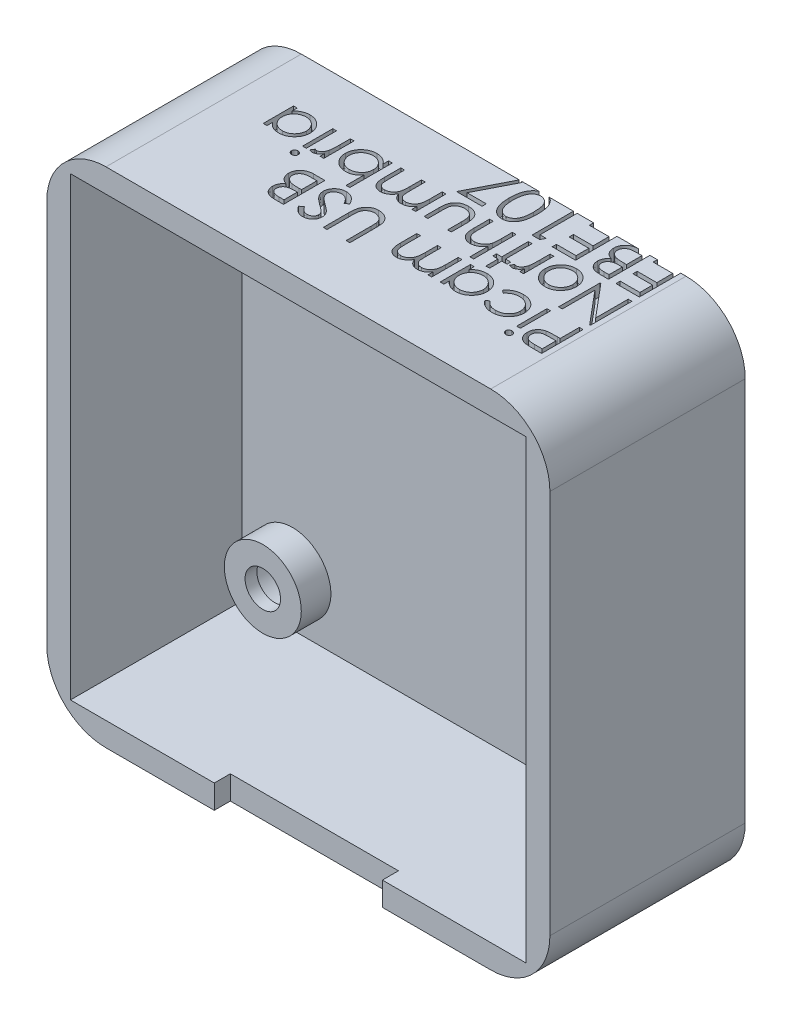
SolidWorks part; units mm, degrees
ref_plane "Front Plane" through (0, 0, 0) normal (0, 0, 1) x (1, 0, 0)
ref_plane "Top Plane" through (0, 0, 0) normal (0, 1, 0) x (1, 0, 0)
ref_plane "Right Plane" through (0, 0, 0) normal (1, 0, 0) x (0, 0, -1)
sketch "Sketch1" plane through (0, 0, 0) normal (0, 0, 1) x (1, 0, 0)
  line L1 (-20.25, -20.25) -> (20.25, -20.25)
  line L2 (-20.25, -20.25) -> (-20.25, 20.25)
  line L3 (-20.25, 20.25) -> (20.25, 20.25)
  line L4 (20.25, -20.25) -> (20.25, 20.25)
  line L5 (-20.25, -20.25) -> (20.25, 20.25) construction
  line L6 (-20.25, 20.25) -> (20.25, -20.25) construction
  point P0 (0, 0)
extrude "Boss-Extrude1" add sketch "Sketch1" along normal blind 2
sketch "Sketch2" plane through (0, 0, 2) normal (0, 0, 1) x (1, 0, 0)
  circle A0 centre (-15, 15) radius 1.25
  circle A1 centre (15, -15) radius 1.25
  circle A2 centre (15, 16.25) radius 1.25
  circle A3 centre (-15, -15) radius 1.25
extrude "Cut-Extrude1" cut sketch "Sketch2" against normal blind 2 contours A3 | A1 | A2 | A0
sketch "Sketch3" plane through (0, 0, 2) normal (0, 0, 1) x (1, 0, 0)
  line L0 (20.25, 20.25) -> (-20.25, 20.25) construction
  line L5 (-19.25, -19.25) -> (19.25, 19.25) construction
  line L6 (-19.25, 19.25) -> (19.25, -19.25) construction
  line L7 (21.25, -21.25) -> (-21.25, -21.25)
  line L8 (21.25, -21.25) -> (21.25, 21.25)
  line L9 (21.25, 21.25) -> (-21.25, 21.25)
  line L10 (-21.25, -21.25) -> (-21.25, 21.25)
  line L11 (21.25, -21.25) -> (-21.25, 21.25) construction
  line L12 (21.25, 21.25) -> (-21.25, -21.25) construction
  line L13 (20.25, -20.25) -> (-20.25, -20.25)
  line L14 (20.25, -20.25) -> (20.25, 20.25)
  line L15 (20.25, 20.25) -> (-20.25, 20.25)
  line L16 (-20.25, -20.25) -> (-20.25, 20.25)
  line L17 (20.25, -20.25) -> (-20.25, 20.25) construction
  line L18 (20.25, 20.25) -> (-20.25, -20.25) construction
  point P0 (0, 0)
  point P6 (0, 0)
  point P11 (0, 0)
extrude "Boss-Extrude2" add sketch "Sketch3" against normal blind 2
sketch "Sketch4" plane through (0, 0, 2) normal (0, 0, 1) x (1, 0, 0)
  line L1 (21.25, -21.25) -> (-21.25, -21.25)
  line L2 (21.25, -21.25) -> (21.25, 21.25)
  line L3 (21.25, 21.25) -> (-21.25, 21.25)
  line L4 (-21.25, -21.25) -> (-21.25, 21.25)
  line L5 (21.25, -21.25) -> (-21.25, 21.25) construction
  line L6 (21.25, 21.25) -> (-21.25, -21.25) construction
  line L7 (19.25, -19.25) -> (-19.25, -19.25)
  line L8 (19.25, -19.25) -> (19.25, 19.25)
  line L9 (19.25, 19.25) -> (-19.25, 19.25)
  line L10 (-19.25, -19.25) -> (-19.25, 19.25)
  line L11 (19.25, -19.25) -> (-19.25, 19.25) construction
  line L12 (19.25, 19.25) -> (-19.25, -19.25) construction
  point P0 (0, 0)
  point P7 (0, 0)
extrude "Boss-Extrude3" add sketch "Sketch4" along normal blind 14.5
sketch "Sketch6" plane through (0, 0, 2) normal (0, 0, 1) x (1, 0, 0)
  circle A0 centre (-15, 15) radius 2.25
  circle A1 centre (-15, 15) radius 3.25
  circle A3 centre (15, 15) radius 3.25
  circle A4 centre (15, 16.25) radius 1.25 construction
  circle A5 centre (15, 15) radius 2.25
  circle A6 centre (-15, -15) radius 2.25
  circle A7 centre (-15, -15) radius 3.25
  circle A8 centre (15, -15) radius 2.25
  circle A9 centre (15, -15) radius 3.25
extrude "Boss-Extrude4" add sketch "Sketch6" along normal blind 2.5
sketch "Sketch7" plane through (0, 0, 0) normal (0, 0, -1) x (-1, 0, 0)
  circle A0 centre (-15, 16.25) radius 1.25
extrude "Boss-Extrude5" add sketch "Sketch7" against normal blind 2
sketch "Sketch8" plane through (0, 0, 2) normal (0, 0, 1) x (1, 0, 0)
  circle A0 centre (15, 15) radius 1.25
extrude "Cut-Extrude2" cut sketch "Sketch8" against normal blind 2
sketch "Sketch10" plane through (0, 0, 4.5) normal (0, 0, 1) x (1, 0, 0)
  circle A0 centre (-15, 15) radius 2.25
  circle A1 centre (15, 15) radius 2.25
  circle A2 centre (15, 15) radius 1.25
  circle A3 centre (-15, 15) radius 1.25
  circle A4 centre (-15, -15) radius 1.25
  circle A5 centre (-15, -15) radius 2.25
  circle A6 centre (15, -15) radius 1.25
  circle A7 centre (15, -15) radius 2.25
extrude "Boss-Extrude6" add sketch "Sketch10" against normal blind 1
sketch "Sketch11" plane through (0, 0, 0) normal (0, 0, -1) x (-1, 0, 0)
  circle A0 centre (-15, 15) radius 2.25
  circle A1 centre (15, 15) radius 2.25
  circle A2 centre (15, -15) radius 2.25
  circle A3 centre (-15, -15) radius 2.25
extrude "Cut-Extrude3" cut sketch "Sketch11" against normal blind 3.5
sketch "Sketch12" plane through (0, 0, 0) normal (0, 0, -1) x (-1, 0, 0)
  line L11 (-10.8, 15.2) -> (-3.3, 15.2)
  line L12 (-10.8, 15.2) -> (-10.8, 11.7)
  line L13 (-10.8, 11.7) -> (-3.3, 11.7)
  line L14 (-3.3, 15.2) -> (-3.3, 11.7)
  point P0 (0, 0)
extrude "Cut-Extrude4" cut sketch "Sketch12" against normal blind 3.5
sketch "Sketch13" plane through (0, 0, 0) normal (0, 0, -1) x (-1, 0, 0)
  line L4 (-11.05, 11.45) -> (-3.05, 11.45)
  line L5 (-11.05, 11.45) -> (-11.05, 15.45)
  line L6 (-11.05, 15.45) -> (-3.05, 15.45)
  line L7 (-3.05, 11.45) -> (-3.05, 15.45)
  point P4 (-7.05, 13.45)
extrude "Cut-Extrude5" cut sketch "Sketch13" against normal blind 3.5 contours L6 L7 L4 L5
sketch "Sketch14" plane through (0, 0, 0) normal (0, 0, -1) x (-1, 0, 0)
  circle A0 centre (14, 7) radius 1.5
  point P0 (0, 0)
extrude "Cut-Extrude6" cut sketch "Sketch14" against normal blind 3.5
sketch "Sketch15" plane through (0, 0, 0) normal (0, 0, -1) x (-1, 0, 0)
  circle A0 centre (-15, 15) radius 1.5
  circle A1 centre (15, 15) radius 1.5
  circle A2 centre (-15, -15) radius 1.5
  circle A3 centre (15, -15) radius 1.5
extrude "Cut-Extrude7" cut sketch "Sketch15" against normal blind 12
sketch "Sketch16" plane through (0, 0, 0) normal (0, 0, -1) x (-1, 0, 0)
  circle A0 centre (-15, 15) radius 2.5
  circle A1 centre (15, 15) radius 2.5
  circle A2 centre (-15, -15) radius 2.5
  circle A3 centre (15, -15) radius 2.5
extrude "Cut-Extrude10" cut sketch "Sketch16" against normal blind 3.5 contours A2 | A3 | A1 | A0
sketch "Sketch17" plane through (0, -21.25, 0) normal (0, -1, 0) x (1, 0, 0)
  line L0 (-21.25, 16.5) -> (21.25, 16.5) construction
  line L1 (-7.1, 17.8563) -> (7.1, 17.8563)
  line L2 (-7.1, 17.8563) -> (-7.1, 15.1437)
  line L3 (-7.1, 15.1437) -> (7.1, 15.1437)
  line L4 (7.1, 17.8563) -> (7.1, 15.1437)
  line L5 (-7.1, 17.8563) -> (7.1, 15.1437) construction
  line L6 (-7.1, 15.1437) -> (7.1, 17.8563) construction
  point P0 (0, 16.5)
extrude "Cut-Extrude11" cut sketch "Sketch17" against normal blind 3.5
fillet "Fillet1" radius 5 4 edges at (-21.25, -21.25, 8.25) (-21.25, 21.25, 8.25) (21.25, 21.25, 8.25) (21.25, -21.25, 8.25)
sketch "Sketch18" plane through (0, 21.25, 0) normal (0, 1, 0) x (1, 0, 0)
  line L0 (16.25, -8.25) -> (-16.25, -8.25) construction
  line L1 (16.25, -16.5) -> (16.25, 0) construction
  line L2 (-16.25, 0) -> (-16.25, -16.5) construction
  line L3 (16.25, -8.25) -> (16.25, 0) construction
  line L4 (16.25, 0) -> (-16.25, 0) construction
  line L5 (16.25, -4.125) -> (-16.25, -4.125) construction
  line L6 (16.25, 0) -> (-16.25, 0) construction
  text T0 "Picam USB"
  text T1 "Northumbria"
  text T2 "EBE107"
extrude "Cut-Extrude13" cut sketch "Sketch18" against normal blind 1
